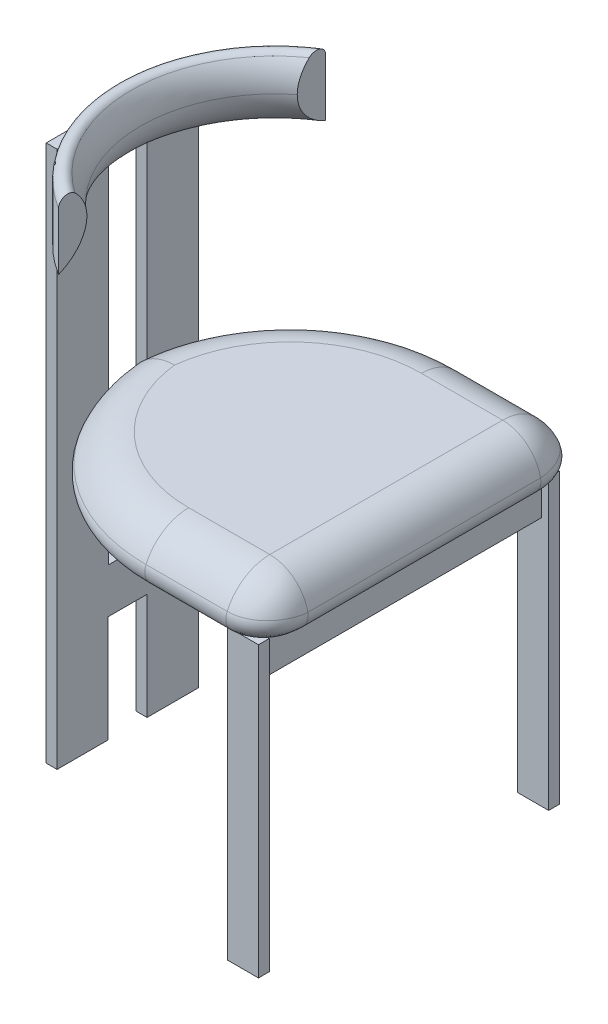
SolidWorks part; units mm, degrees
ref_plane "Front Plane" through (0, 0, 0) normal (0, 0, 1) x (1, 0, 0)
ref_plane "Top Plane" through (0, 0, 0) normal (0, 1, 0) x (1, 0, 0)
ref_plane "Right Plane" through (0, 0, 0) normal (1, 0, 0) x (0, 0, -1)
sketch "Sketch1" plane through (0, 0, 0) normal (0, 1, 0) x (1, 0, 0)
  line L0 (0, 0) -> (0, 338.1895)
  line L1 (0, 338.1895) -> (0, -195.2105)
  arc A0 (0, 338.1895) -> (0, -195.2105) centre (-170.2572, 71.4895) ccw
  dimension "D2" = 533.4
extrude "Boss-Extrude1" add sketch "Sketch1" along normal mid plane 17.78 contours L0 A0 L1 region at (-218.9822, 0, -71.4895)
sketch "Sketch2" plane through (0, -8.89, 0) normal (0, -1, 0) x (1, 0, 0)
  line L0 (-486.669, -71.4895) -> (-486.669, -350.6067) construction
  line L1 (-486.669, -350.6067) -> (-486.669, 186.5621) construction
  arc A0 (0, 195.2105) -> (0, -338.1895) centre (-170.2572, -71.4895) ccw construction
ref_plane "Plane1" through (-486.669, 0, 0) normal (-1, 0, 0) x (0, 0, 1)
sketch "Sketch4" plane through (0, -8.89, 0) normal (0, -1, 0) x (1, 0, 0)
  line L0 (0, 195.2105) -> (0, -338.1895) construction
  line L1 (-50.8, 157.1105) -> (-38.1, 157.1105)
  line L2 (-50.8, 157.1105) -> (-50.8, -300.0895)
  line L3 (-50.8, -300.0895) -> (-38.1, -300.0895)
  line L4 (-38.1, 157.1105) -> (-38.1, -300.0895)
  line L5 (-50.8, 108.2066) -> (-486.669, -15.944)
  line L6 (-486.669, -350.6067) -> (-486.669, 186.5621) construction
  line L7 (-50.8, 95.0015) -> (-483.19, -28.1582)
  line L8 (-47.321, 95.9924) -> (-483.19, -28.1582) construction
  line L9 (-483.19, -28.1582) -> (-486.669, -29.1491)
  line L10 (-486.669, -71.4895) -> (141.6059, -71.4895) construction
  line L11 (-50.8, -251.1855) -> (-486.669, -127.0349)
  line L12 (-50.8, -237.9804) -> (-483.19, -114.8208)
  line L13 (-483.19, -114.8208) -> (-486.669, -113.8298)
  line L14 (-486.669, -71.4895) -> (-486.669, -350.6067) construction
  arc M10 (0, 195.2105) -> (0, -338.1895) centre (-170.2572, -71.4895) ccw
  dimension "D1" = 38.1
  dimension "D2" = 12.7
  dimension "D4" = 228.6
  dimension "D5" = 457.2
  dimension "D3" = 12.7
extrude "Boss-Extrude2" add sketch "Sketch4" along normal blind 63.5 separate body contours L9 L7 L2 L5 M10 | L12 L13 L11 L2 M10 | L4 L1 L2 L3 region at (-44.45, -8.89, -71.4895) region at (-266.7272, -8.89, 40.0949) region at (-266.7272, -8.89, -183.0738)
sketch "Sketch5" plane through (0, 8.89, 0) normal (0, 1, 0) x (1, 0, 0)
  line L0 (0, 338.1895) -> (-196.2962, 338.1895)
  line L1 (0, 71.4895) -> (-478.526, 71.4895)
  line L2 (0, -195.2105) -> (0, 338.1895) construction
  line L3 (0, -195.2105) -> (-196.2962, -195.2105)
  arc A0 (-196.2962, 338.1895) -> (-486.669, 71.4895) centre (-196.2962, 46.766) ccw
  arc A1 (-196.2962, -195.2105) -> (-486.669, 71.4895) centre (-196.2962, 96.2129) cw
  arc A2 (0, 338.1895) -> (0, -195.2105) centre (-170.2572, 71.4895) ccw construction
  arc A3 (0, 338.1895) -> (0, -195.2105) centre (-170.2572, 71.4895) ccw
  arc M5 (0, 338.1895) -> (0, -195.2105) centre (-170.2572, 71.4895) ccw
extrude "Cut-Extrude1" cut sketch "Sketch5" against normal blind 63.5 and the other way through all contours L3 A1 M5 | A0 L0 M5 region at (-397.3556, 8.89, 122.6929) region at (-98.1481, 8.89, -343.9943)
sketch "Sketch6" plane through (0, 8.89, 0) normal (0, 1, 0) x (1, 0, 0)
  line L0 (0, -195.2105) -> (0, 338.1895) construction
  line L1 (-196.2962, -195.2105) -> (0, -195.2105) construction
  line L2 (0, 338.1895) -> (-196.2962, 338.1895) construction
  line L3 (0, -195.2105) -> (0, 338.1895)
  line L4 (-196.2962, -195.2105) -> (0, -195.2105)
  line L5 (0, 338.1895) -> (-196.2962, 338.1895)
  arc A0 (-486.669, 71.4895) -> (-196.2962, -195.2105) centre (-196.2962, 96.2129) ccw construction
  arc A1 (-196.2962, 338.1895) -> (-486.669, 71.4895) centre (-196.2962, 46.766) ccw construction
  arc A2 (-486.669, 71.4895) -> (-196.2962, -195.2105) centre (-196.2962, 96.2129) ccw
  arc A3 (-196.2962, 338.1895) -> (-486.669, 71.4895) centre (-196.2962, 46.766) ccw
extrude "Boss-Extrude3" add sketch "Sketch6" along normal blind 63.5
fillet "Fillet2" radius 76.2 4 edges at (-98.1481, 72.39, -338.1895) (-393.4289, 72.39, 118.4177) (-393.4289, 72.39, -261.3966) (-98.1481, 72.39, 195.2105)
fillet "Fillet3" radius 63.5 5 edges at (0, -6.35, 195.2105) (0, 50.0715, 172.8921) (0, -6.35, -338.1895) (0, 50.0715, -315.871) (0, 72.39, -71.4895)
fillet "Fillet4" radius 25.4 7 edges at (-393.4289, -8.89, -261.3966) (-129.8981, -8.89, -338.1895) (-18.5987, -8.89, -319.5907) (0, -8.89, -71.4895) (-18.5987, -8.89, 176.6118) (-129.8981, -8.89, 195.2105) (-393.4289, -8.89, 118.4177)
sketch "Sketch7" plane through (-486.669, 0, 0) normal (-1, 0, 0) x (0, 0, 1)
  line L0 (-39.7395, 397.9721) -> (-39.7395, 72.39)
  line L1 (-71.4895, -8.89) -> (-71.4895, 184.4665) construction
  line L2 (-71.4895, 184.4665) -> (-71.4895, -147.3888) construction
  line L4 (119.0105, 72.39) -> (-71.4895, 72.39) construction
  line L5 (-39.7395, 397.9721) -> (44.0805, 397.9721)
  line L6 (44.0805, 397.9721) -> (44.0805, -504.19)
  line L7 (157.1105, -72.39) -> (108.2066, -72.39) construction
  line L8 (44.0805, -504.19) -> (-39.2096, -504.19)
  line L9 (-39.2096, -504.19) -> (-39.2096, -306.6568)
  line L10 (-39.2096, -306.6568) -> (-103.2395, -306.6568)
  line L11 (-103.2395, -306.6568) -> (-103.2395, -504.19)
  line L12 (-103.2395, -504.19) -> (-187.0595, -504.19)
  line L13 (-187.0595, -504.19) -> (-187.0595, 397.9721)
  line L14 (-187.0595, 397.9721) -> (-103.2395, 397.9721)
  line L15 (-103.2395, 397.9721) -> (-103.2395, -233.3679)
  line L16 (-103.2395, -233.3679) -> (-39.7395, -233.3679)
  line L17 (-39.7395, -233.3679) -> (-39.7395, 72.39)
  dimension "D2" = 431.8
  dimension "D3" = 83.82
  dimension "D4" = 83.82
  dimension "D5" = 31.75
  dimension "D6" = 31.75
extrude "Boss-Extrude4" add sketch "Sketch7" along normal blind 17.78 separate body
sketch "Sketch8" plane through (0, 0, 157.1105) normal (0, 0, 1) x (1, 0, 0)
  line L0 (-63.5, -8.89) -> (-26.1698, -8.89) construction
  line L1 (-26.1698, -8.89) -> (-76.9698, -8.89)
  line L2 (-26.1698, -8.89) -> (-26.1698, -504.1022)
  line L3 (-26.1698, -504.1022) -> (-76.9698, -504.1022)
  line L4 (-76.9698, -8.89) -> (-76.9698, -504.1022)
  line L5 (-486.669, -504.19) -> (93.7152, -504.19) construction
  arc A0 (-26.1698, -8.89) -> (-1.283, 21.59) centre (-26.1698, 16.51) ccw construction
  dimension "D1" = 50.8
extrude "Boss-Extrude5" add sketch "Sketch8" along normal blind 17.78 separate body
sketch "Sketch9" plane through (0, 0, -300.0895) normal (0, 0, -1) x (-1, 0, 0)
  line L1 (26.1698, -8.89) -> (76.9698, -8.89)
  line L2 (26.1698, -8.89) -> (26.1698, -504.1022)
  line L3 (26.1698, -504.1022) -> (76.9698, -504.1022)
  line L4 (76.9698, -8.89) -> (76.9698, -504.1022)
extrude "Boss-Extrude6" add sketch "Sketch9" along normal blind 17.78 separate body
sketch "Sketch10" plane through (0, 397.9721, 0) normal (0, 1, 0) x (1, 0, 0)
  line L0 (-380.348, 289.12) -> (-380.348, 242.7138)
  line L2 (-380.348, -101.6102) -> (-380.348, -148.0164)
  arc A0 (-380.348, 289.12) -> (-380.348, -148.0164) centre (-245.1423, 70.5518) ccw
  arc A1 (-380.348, 242.7138) -> (-380.348, -101.6102) centre (-245.1423, 70.5518) ccw
  arc A2 (-360.3045, 256.7184) -> (-360.3045, -115.6148) centre (-245.1423, 70.5518) ccw construction
  dimension "D1" = 38.1
extrude "Boss-Extrude7" add sketch "Sketch10" along normal blind 46.736 and the other way blind 72.644
fillet "Fillet6" radius 66.04 2 edges at (-464.0494, 444.7081, -70.5518) (-464.0494, 325.3281, -70.5518)
fillet "Fillet7" radius 12.7 1 edges at (-502.1494, 444.7081, -70.5518)
sketch "Sketch11" plane through (-26.1698, 0, 0) normal (1, 0, 0) x (0, 0, -1)
  line L0 (317.8695, -8.89) -> (317.8695, -504.1022) construction
  line L1 (-174.8905, -504.1022) -> (317.8695, -504.1022)
  line L2 (-174.8905, -504.1022) -> (-174.8905, -481.3329)
  line L3 (-174.8905, -481.3329) -> (317.8695, -481.3329)
  line L4 (317.8695, -504.1022) -> (317.8695, -481.3329)
extrude "Cut-Extrude2" cut sketch "Sketch11" against normal through all
sketch "Sketch12" plane through (-504.449, 0, 0) normal (-1, 0, 0) x (0, 0, 1)
  line L1 (-196.6148, -495.3548) -> (73.1147, -495.3548)
  line L2 (-196.6148, -495.3548) -> (-196.6148, -510.9882)
  line L3 (-196.6148, -510.9882) -> (73.1147, -510.9882)
  line L4 (73.1147, -495.3548) -> (73.1147, -510.9882)
extrude "Cut-Extrude3" cut sketch "Sketch12" against normal through all
